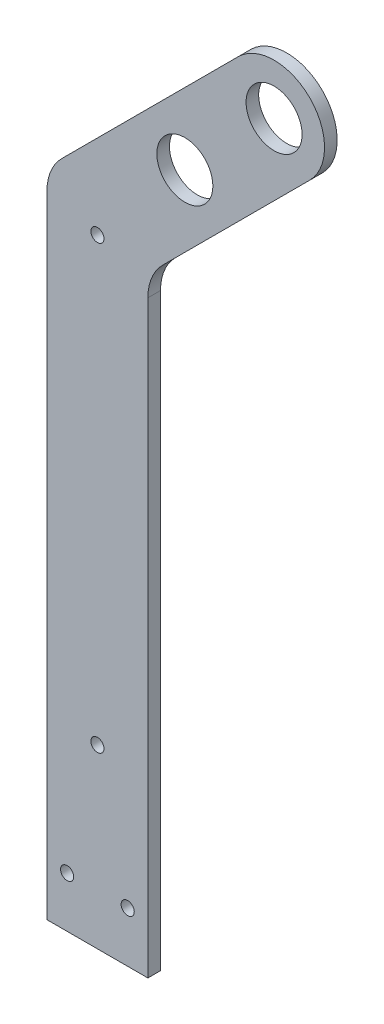
SolidWorks part; units mm, degrees
material "6061 合金"
ref_plane "前视基准面" through (0, 0, 0) normal (0, 0, 1) x (1, 0, 0)
ref_plane "上视基准面" through (0, 0, 0) normal (0, 1, 0) x (1, 0, 0)
ref_plane "右视基准面" through (0, 0, 0) normal (1, 0, 0) x (0, 0, -1)
other "Configuration Table"
sketch "草图1" plane through (0, 0, 0) normal (0, 0, 1) x (1, 0, 0)
  circle A0 centre (0, 0) radius 20
  circle A1 centre (0, 0) radius 11.1
  dimension "D1" = 40
  dimension "D2" = 22.2
extrude "凸台-拉伸1" add sketch "草图1" along normal blind 60 contours A1 | A0 region at (0, 0, 0)
ref_plane "基准面1" through (0, 0, 30) normal (0, 0, 1) x (1, 0, 0)
sketch "草图2" plane through (0, 0, 30) normal (0, 0, 1) x (1, 0, 0)
  line L0 (0, 0) -> (-70, -70) construction
  line L1 (-70, -70) -> (-70, -320) construction
  line L2 (0, -57.3148) -> (0, 49.9409) construction
  line L3 (-56.8582, 0) -> (46.4003, 0) construction
  line L4 (-14.1421, 14.1421) -> (-90, -61.7157)
  line L5 (14.1421, -14.1421) -> (-50, -78.2843)
  line L6 (-90, -61.7157) -> (-90, -320)
  line L7 (-50, -78.2843) -> (-50, -320)
  line L8 (-90, -320) -> (-50, -320)
  circle A2 centre (0, 0) radius 20 construction
  arc A3 (-14.1421, 14.1421) -> (14.1421, -14.1421) centre (0, 0) ccw
  dimension "D1" = 45
  dimension "D2" = 250
  dimension "D3" = 70
  dimension "D4" = 40
  dimension "D5" = 40
extrude "凸台-拉伸2" add sketch "草图2" along normal mid plane 60 contours L7 L8 L6 L4 A3 L5
sketch "草图4" plane through (0, 0, 60) normal (0, 0, 1) x (1, 0, 0)
  line L0 (-90, -61.7157) -> (-90, -320) construction
  line L1 (-90, -290) -> (-50, -290)
  line L2 (-90, -290) -> (-90, -350)
  line L4 (-50, -290) -> (-50, -350)
  line L5 (-50, -78.2843) -> (-50, -320) construction
  line L6 (-90, -320) -> (-50, -320) construction
  arc A0 (-90, -350) -> (-50, -350) centre (-70, -350) ccw
  circle A1 centre (-70, -350) radius 11
  dimension "D3" = 22
  dimension "D1" = 30
  dimension "D2" = 30
extrude "凸台-拉伸3" add sketch "草图4" along normal blind 5
mirror "镜向1" about plane through (0, 0, 30) normal (0, 0, 1) of "凸台-拉伸3"
sketch "草图5" plane through (0, 0, 0) normal (0, 1, 0) x (1, 0, 0)
  line L0 (0, 0) -> (0, -78.0582) construction
ref_plane "基准面2" through (-70, 0, 0) normal (-1, 0, 0) x (0, 0, 1)
sketch "草图7" plane through (-70, 0, 0) normal (-1, 0, 0) x (0, 0, 1)
  line L0 (-34.1239, -350) -> (109.535, -350) construction
sketch "草图8" plane through (0, 0, 60) normal (0, 0, 1) x (1, 0, 0)
  line L0 (0, 0) -> (-70, -70) construction
  circle A0 centre (-35.3553, -35.3553) radius 11.1
  dimension "D1" = 22.2
  dimension "D2" = 50
extrude "切除-拉伸1" cut sketch "草图8" against normal blind 100
fillet "圆角4" radius 20 2 edges at (-90, -61.7157, 30) (-50, -78.2843, 30)
fillet "圆角1" [suppressed] radius 50
fillet "圆角2" [suppressed] radius 3
sketch "草图9" plane through (0, 0, 65) normal (0, 0, 1) x (1, 0, 0)
  circle A0 centre (-70, -350) radius 13
  dimension "D1" = 26
extrude "切除-拉伸2" [suppressed] cut sketch "草图9" against normal blind 0.75
sketch "草图10" plane through (0, 0, -5) normal (0, 0, -1) x (-1, 0, 0)
  circle A0 centre (70, -350) radius 13
  dimension "D1" = 26
extrude "切除-拉伸3" [suppressed] cut sketch "草图10" against normal blind 0.75 contours A0
sketch "草图11" plane through (-90, 0, 0) normal (-1, 0, 0) x (0, 0, 1)
  circle A0 centre (48.5, -118.9949) radius 2.75
  circle A1 centre (48.5, -183.9949) radius 2.75
  circle A2 centre (48.5, -248.9949) radius 2.75
  circle A3 centre (11.5, -248.9949) radius 2.75
  circle A4 centre (11.5, -183.9949) radius 2.75
  circle A5 centre (11.5, -118.9949) radius 2.75
  dimension "D1" = 5.5
extrude "切除-拉伸4" [suppressed] cut sketch "草图11" against normal through all contours A1 | A2 | A0 | A3 | A4 | A5
sketch "草图12" [suppressed] plane through (-90, 0, 0) normal (-1, 0, 0) x (0, 0, 1)
  line L0 (30, -62.0134) -> (30, -339.6946) construction
  line L1 (10, -128.9949) -> (50, -128.9949)
  line L2 (10, -128.9949) -> (10, -173.9949)
  line L3 (10, -173.9949) -> (50, -173.9949)
  line L4 (50, -128.9949) -> (50, -173.9949)
  line L5 (10, -193.9949) -> (50, -193.9949)
  line L6 (10, -193.9949) -> (10, -238.9949)
  line L7 (10, -238.9949) -> (50, -238.9949)
  line L8 (50, -193.9949) -> (50, -238.9949)
  line L9 (10, -258.9949) -> (50, -258.9949)
  line L10 (10, -258.9949) -> (10, -290)
  line L11 (10, -290) -> (50, -290)
  line L12 (50, -258.9949) -> (50, -290)
  line L13 (19.5, -173.9949) -> (40.5, -173.9949)
  line L14 (19.5, -173.9949) -> (19.5, -193.9949)
  line L15 (19.5, -193.9949) -> (40.5, -193.9949)
  line L16 (40.5, -173.9949) -> (40.5, -193.9949)
  line L17 (19.5, -238.9949) -> (40.5, -238.9949)
  line L18 (19.5, -238.9949) -> (19.5, -258.9949)
  line L19 (19.5, -258.9949) -> (40.5, -258.9949)
  line L20 (40.5, -238.9949) -> (40.5, -258.9949)
  line L21 (60, -82.4264) -> (60, -290) construction
  line L22 (0, -290) -> (0, -82.4264) construction
  line L23 (57, -320) -> (3, -320) construction
  circle A0 centre (48.5, -118.9949) radius 2.75 construction
  circle A1 centre (48.5, -183.9949) radius 2.75 construction
  circle A2 centre (48.5, -248.9949) radius 2.75 construction
  dimension "D1" = 10
  dimension "D2" = 10
  dimension "D3" = 10
  dimension "D4" = 8
  dimension "D5" = 10
  dimension "D6" = 10
  dimension "D7" = 10
  dimension "D8" = 30
extrude "减重" [suppressed] cut sketch "草图12" against normal through all contours L0 L1 L2 L3 | L15 L0 L17 L7 L8 L5 | L0 L5 L6 L7 | L19 L0 L11 L12 L9 | L0 L9 L10 L11 | L1 L0 L13 L3 L4
fillet "圆角3" [suppressed] radius 3
sketch "草图13" plane through (0, 0, 60) normal (0, 0, 1) x (1, 0, 0)
  circle A0 centre (0, 0) radius 13
  circle A1 centre (-35.3553, -35.3553) radius 13
  dimension "D1" = 26
  dimension "D2" = 26
extrude "切除-拉伸6" [suppressed] cut sketch "草图13" against normal blind 1.75
sketch "草图14" plane through (0, 0, 0) normal (0, 0, -1) x (-1, 0, 0)
  circle A0 centre (0, 0) radius 13
  circle A1 centre (35.3553, -35.3553) radius 13
  dimension "D1" = 26
  dimension "D2" = 26
extrude "切除-拉伸7" [suppressed] cut sketch "草图14" against normal blind 1.75
sketch "草图15" [suppressed] plane through (0, 0, 0) normal (0, 0, -1) x (-1, 0, 0)
  line L0 (0, 0) -> (70, -350) construction
  line L1 (56.2719, -67.2005) -> (60.1942, -86.8121) construction
  line L2 (70, -350) -> (204.3541, -323.1292) construction
  circle A0 centre (56.2719, -67.2005) radius 2.75
  circle A1 centre (75.2172, -73.6095) radius 2.75
  circle A2 centre (60.1942, -86.8121) radius 2.75
  dimension "D1" = 5.5
  dimension "D2" = 20
  dimension "D3" = 20
  dimension "D4" = 20
  dimension "D5" = 42
  dimension "D6" = 270
extrude "切除-拉伸8" [suppressed] cut sketch "草图15" against normal through all contours A2 | A0 | A1
ref_plane "小腿主干连杆面" through (0, 0, 0) normal (0.9806, -0.1961, 0) x (0, 0, -1)
ref_plane "小腿主干对称面" through (0, 0, 30) normal (0, 0, -1) x (-1, 0, 0)
sketch "草图16" plane through (0, 0, 60) normal (0, 0, 1) x (1, 0, 0)
  line L0 (0, 0) -> (-70, -350)
  line L1 (-35.3553, -35.3553) -> (0, 0)
sketch "草图17" plane through (0, 0, 60) normal (0, 0, 1) x (1, 0, 0)
  line L0 (0, 0) -> (-70, -350) construction
  line L1 (118.6974, 32.5948) -> (32.9122, -396.3312) construction
  line L2 (92.7764, -97.0102) -> (20.2919, -82.5133)
  line L3 (73.1648, -195.0683) -> (0.6803, -180.5713)
  circle A0 centre (20.2919, -82.5133) radius 46
  circle A1 centre (0.6803, -180.5713) radius 46
  dimension "D3" = 92
  dimension "D4" = 92
  dimension "D1" = 110
  dimension "D2" = 73.92
  dimension "D5" = 180
  dimension "D6" = 280
sketch "草图18" plane through (0, 0, 60) normal (0, 0, 1) x (1, 0, 0)
  line L1 (14.1421, -14.1421) -> (-44.1421, -72.4264) construction
  line L3 (14.1421, -14.1421) -> (-44.1421, -72.4264)
  line L4 (15.4873, -12.6548) -> (52.8188, -49.9864)
  line L5 (-50, -128.5133) -> (20.2919, -128.5133)
  line L10 (-90, -290) -> (-50, -290)
  line L11 (-50, -290) -> (-50, -86.5685)
  line L12 (-44.1421, -72.4264) -> (14.1421, -14.1421)
  line L13 (-14.1421, 14.1421) -> (-84.1421, -55.8579)
  line L14 (-90, -70) -> (-90, -290)
  line L16 (-50, -128.5133) -> (-50, -86.5685)
  line L17 (-44.1421, -72.4264) -> (14.1421, -14.1421)
  circle A0 centre (20.2919, -82.5133) radius 46 construction
  arc A1 (14.1421, -14.1421) -> (-14.1421, 14.1421) centre (0, 0) ccw construction
  arc A2 (14.1421, -14.1421) -> (-14.1421, 14.1421) centre (0, 0) ccw
  arc A3 (14.1421, -14.1421) -> (15.4873, -12.6548) centre (0, 0) ccw
  arc A4 (20.2919, -128.5133) -> (52.8188, -49.9864) centre (20.2919, -82.5133) ccw
  circle A5 centre (20.2919, -82.5133) radius 35
  arc A9 (-84.1421, -55.8579) -> (-90, -70) centre (-70, -70) ccw
  arc A10 (-84.1421, -55.8579) -> (-90, -70) centre (-70, -70) ccw
  arc A11 (-44.1421, -72.4264) -> (-50, -86.5685) centre (-30, -86.5685) ccw
  arc A12 (-44.1421, -72.4264) -> (-50, -86.5685) centre (-30, -86.5685) ccw
  line M14 (-50, -290) -> (-50, -86.5685)
  line M15 (-44.1421, -72.4264) -> (14.1421, -14.1421)
  arc M16 (14.1421, -14.1421) -> (-14.1421, 14.1421) centre (0, 0) ccw
  arc M22 (-50, -86.5685) -> (-44.1421, -72.4264) centre (-30, -86.5685) cw
  dimension "D2" = 70
  dimension "D1" = 0
extrude "凸台-拉伸4" add sketch "草图18" against normal blind 5 from offset 25 contours L5 A4 L4 A5 M16 M15 M22 M14 region at (16.0508, -14.5165, 60) offset against normal yes
sketch "草图19" plane through (0, 0, 0) normal (0, 0, -1) x (-1, 0, 0)
  line L0 (50, -86.5685) -> (50, -290) construction
  line L1 (50, -134.5713) -> (50, -226.5713)
  line L2 (-0.6803, -134.5713) -> (50, -134.5713)
  line L3 (-0.6803, -226.5713) -> (50, -226.5713)
  circle A0 centre (-0.6803, -180.5713) radius 46 construction
  arc A1 (-0.6803, -134.5713) -> (-0.6803, -226.5713) centre (-0.6803, -180.5713) ccw
  circle A2 centre (-0.6803, -180.5713) radius 35
  dimension "D1" = 70
extrude "凸台-拉伸5" add sketch "草图19" against normal blind 5 from offset 25 offset against normal yes
fillet "圆角5" radius 10 2 edges at (-50, -226.5713, 27.5) (-50, -128.5133, 32.5)
sketch "草图21" plane through (0, 0, 65) normal (0, 0, 1) x (1, 0, 0)
  line L0 (-70, -350) -> (-70, -6.9331) construction
  circle A0 centre (-70, -75) radius 2.6
  circle A1 centre (-70, -250) radius 2.6
  circle A2 centre (-58, -300) radius 2.6
  circle A3 centre (-82, -300) radius 2.6
  dimension "D1" = 5.2
  dimension "D2" = 12
  dimension "D3" = 50
  dimension "D4" = 100
  dimension "D5" = 175
extrude "切除-拉伸9" cut sketch "草图21" against normal through all both and the other way through all
sketch "草图22" plane through (-90, 0, 0) normal (-1, 0, 0) x (0, 0, 1)
  line L0 (-5, -350) -> (-5, -370) construction
  line L5 (-5, -380.1184) -> (0, -380.1184)
  line L6 (-5, -380.1184) -> (-5, 64.9179)
  line L7 (-5, 64.9179) -> (0, 64.9179)
  line L8 (0, -380.1184) -> (0, 64.9179)
  line L10 (65, -370) -> (5, -370)
  line L11 (65, -370) -> (65, 61.088)
  line L12 (65, 61.088) -> (5, 61.088)
  line L13 (5, -370) -> (5, 61.088)
  point P4 (-5, -380.1184)
  dimension "D1" = 60
  dimension "D2" = 5
extrude "切除-拉伸10" cut sketch "草图22" against normal through all both contours L8 L7 L6 L5 | L13 L12 L11 L10
